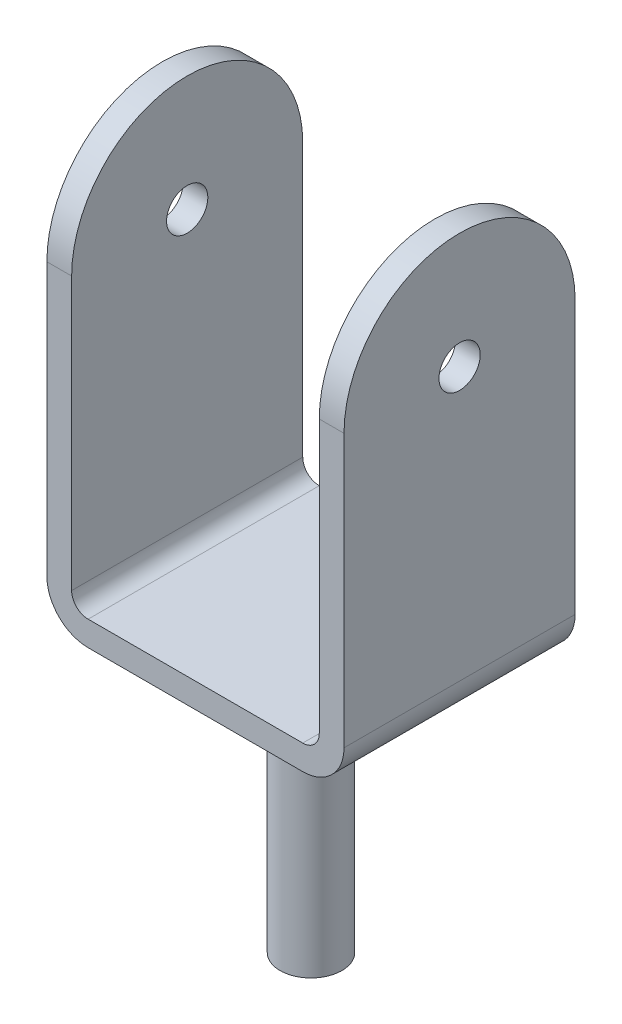
SolidWorks part; units mm, degrees
ref_plane "Front Plane" through (0, 0, 0) normal (0, 0, 1) x (1, 0, 0)
ref_plane "Top Plane" through (0, 0, 0) normal (0, 1, 0) x (1, 0, 0)
ref_plane "Right Plane" through (0, 0, 0) normal (1, 0, 0) x (0, 0, -1)
sketch "Sketch1" plane through (0, 0, 0) normal (0, 0, 1) x (1, 0, 0)
  line L0 (0, 0) -> (0, 490)
  line L1 (0, 490) -> (-30, 490)
  line L2 (-30, 490) -> (-30, -30)
  line L3 (-30, -30) -> (330, -30)
  line L4 (330, -30) -> (330, 490)
  line L5 (330, 490) -> (300, 490)
  line L6 (300, 490) -> (300, 0)
  line L7 (300, 0) -> (0, 0)
  line L8 (-30, 350) -> (0, 350) construction
  point P11 (150, -30)
  dimension "D1" = 30
  dimension "D2" = 360
  dimension "D3" = 30
  dimension "D4" = 140
  dimension "D5" = 380
extrude "Boss-Extrude1" add sketch "Sketch1" along normal blind 280
sketch "Sketch2" plane through (0, -30, 0) normal (0, -1, 0) x (1, 0, 0)
  line L0 (150, 280) -> (150, 0) construction
  line L1 (-30, 280) -> (330, 280) construction
  line L2 (-30, 0) -> (330, 0) construction
  circle A0 centre (150, 140) radius 37.5
  dimension "D1" = 75
extrude "Boss-Extrude2" add sketch "Sketch2" along normal blind 325
sketch "Sketch3" plane through (-30, 0, 0) normal (-1, 0, 0) x (0, 0, 1)
  line L0 (0, 350) -> (280, 350)
  line L1 (0, 490) -> (0, -30) construction
  line L2 (280, 490) -> (280, -30) construction
  line L4 (280, -30) -> (0, -30) construction
  dimension "D1" = 380
sketch "Sketch4" plane through (-30, 0, 0) normal (-1, 0, 0) x (0, 0, 1)
  line L0 (0, 350) -> (280, 350) construction
  arc A0 (0, 350) -> (280, 350) centre (140, 350) cw
extrude "Cut-Extrude2" cut sketch "Sketch4" against normal through all and the other way through all
sketch "Sketch5" plane through (-30, 0, 0) normal (-1, 0, 0) x (0, 0, 1)
  line L0 (0, 350) -> (280, 350) construction
  circle A0 centre (140, 350) radius 25
  dimension "D1" = 50
extrude "Cut-Extrude3" cut sketch "Sketch5" against normal through all both and the other way through all
fillet "Fillet1" radius 50 2 edges at (330, -30, 140) (-30, -30, 140)
fillet "Fillet2" radius 20 2 edges at (0, 0, 140) (300, 0, 140)
